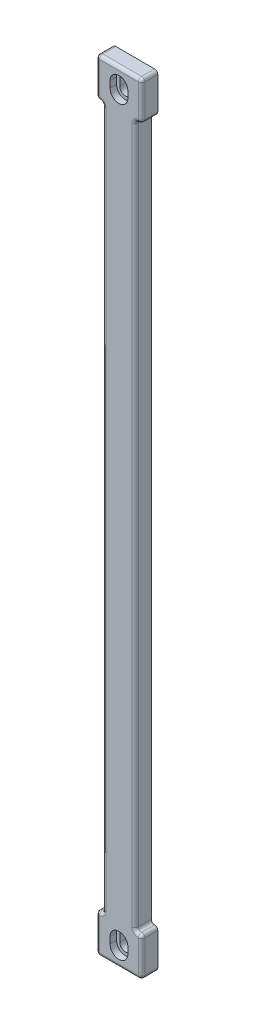
SolidWorks part; units mm, degrees
ref_plane "Front Plane" through (0, 0, 0) normal (0, 0, 1) x (1, 0, 0)
ref_plane "Top Plane" through (0, 0, 0) normal (0, 1, 0) x (1, 0, 0)
ref_plane "Right Plane" through (0, 0, 0) normal (1, 0, 0) x (0, 0, -1)
sketch "Sketch1" plane through (0, 0, 0) normal (0, 0, 1) x (1, 0, 0)
  line L0 (0, 0) -> (14, 0)
  line L1 (14, 0) -> (14, 241)
  line L2 (14, 241) -> (0, 241)
  line L3 (0, 241) -> (0, 0)
  dimension "D1" = 241
  dimension "D2" = 14
extrude "Boss-Extrude1" add sketch "Sketch1" along normal blind 5
sketch "Sketch4" plane through (0, 0, 5) normal (0, 0, 1) x (1, 0, 0)
  line L0 (0, 229) -> (2, 229)
  line L1 (0, 241) -> (0, 0) construction
  line L2 (2, 229) -> (2, 12)
  line L3 (2, 12) -> (0, 12)
  line L4 (0, 12) -> (0, 229)
  line L5 (14, 229) -> (12, 229)
  line L6 (14, 0) -> (14, 241) construction
  line L7 (12, 229) -> (12, 12)
  line L8 (12, 12) -> (14, 12)
  line L9 (14, 12) -> (14, 229)
  line L10 (0, 0) -> (14, 0) construction
  line L11 (14, 241) -> (0, 241) construction
  dimension "D1" = 2
  dimension "D2" = 2
  dimension "D3" = 12
  dimension "D4" = 12
  dimension "D5" = 12
  dimension "D6" = 12
extrude "Cut-Extrude3" cut sketch "Sketch4" against normal up to next
sketch "Sketch2" plane through (0, 0, 5) normal (0, 0, 1) x (1, 0, 0)
  line L0 (14, 241) -> (0, 241) construction
  line L1 (0, 0) -> (14, 0) construction
  line L2 (8.75, 7) -> (8.75, 5)
  line L3 (5.25, 7) -> (5.25, 5)
  line L4 (0, 12) -> (0, 0) construction
  line L5 (8.75, 236) -> (8.75, 234)
  line L6 (5.25, 236) -> (5.25, 234)
  line L7 (14, 229) -> (14, 241) construction
  arc A2 (8.75, 7) -> (5.25, 7) centre (7, 7) ccw
  arc A3 (5.25, 5) -> (8.75, 5) centre (7, 5) ccw
  arc A4 (8.75, 236) -> (5.25, 236) centre (7, 236) ccw
  arc A5 (5.25, 234) -> (8.75, 234) centre (7, 234) ccw
  dimension "D1" = 5
  dimension "D2" = 5
  dimension "D5" = 3.5
  dimension "D6" = 3.5
  dimension "D10" = 3.5
  dimension "D11" = 3.5
  dimension "D3" = 7
  dimension "D4" = 7
  dimension "D7" = 2
  dimension "D8" = 2
  dimension "D9" = 2
  dimension "D12" = 2
  dimension "D13" = 2
  dimension "D14" = 2
extrude "Cut-Extrude1" cut sketch "Sketch2" against normal through all
sketch "Sketch3" plane through (0, 0, 5) normal (0, 0, 1) x (1, 0, 0)
  line L0 (9.75, 7) -> (9.75, 5)
  line L1 (4.25, 7) -> (4.25, 5)
  line L2 (9.75, 236) -> (9.75, 234)
  line L3 (4.25, 236) -> (4.25, 234)
  arc A2 (9.75, 7) -> (4.25, 7) centre (7, 7) ccw
  arc A3 (4.25, 5) -> (9.75, 5) centre (7, 5) ccw
  arc A4 (9.75, 236) -> (4.25, 236) centre (7, 236) ccw
  arc A5 (4.25, 234) -> (9.75, 234) centre (7, 234) ccw
  dimension "D1" = 5.5
  dimension "D2" = 5.5
  dimension "D3" = 5.5
  dimension "D6" = 5.5
  dimension "D4" = 2
  dimension "D5" = 2
  dimension "D7" = 2
  dimension "D8" = 2
extrude "Cut-Extrude2" cut sketch "Sketch3" against normal blind 2
fillet "Fillet1" radius 1 20 edges at (0, 241, 2.5) (14, 241, 2.5) (7, 241, 5) (14, 6, 5) (14, 235, 5) (0, 6, 5) (0, 235, 5) (7, 0, 5) (0, 0, 2.5) (14, 0, 2.5) (0, 229, 2.5) (2, 229, 2.5) (12, 229, 2.5) (14, 229, 2.5) (12, 120.5, 5) (12, 12, 2.5) (14, 12, 2.5) (2, 120.5, 5) (2, 12, 2.5) (0, 12, 2.5)
